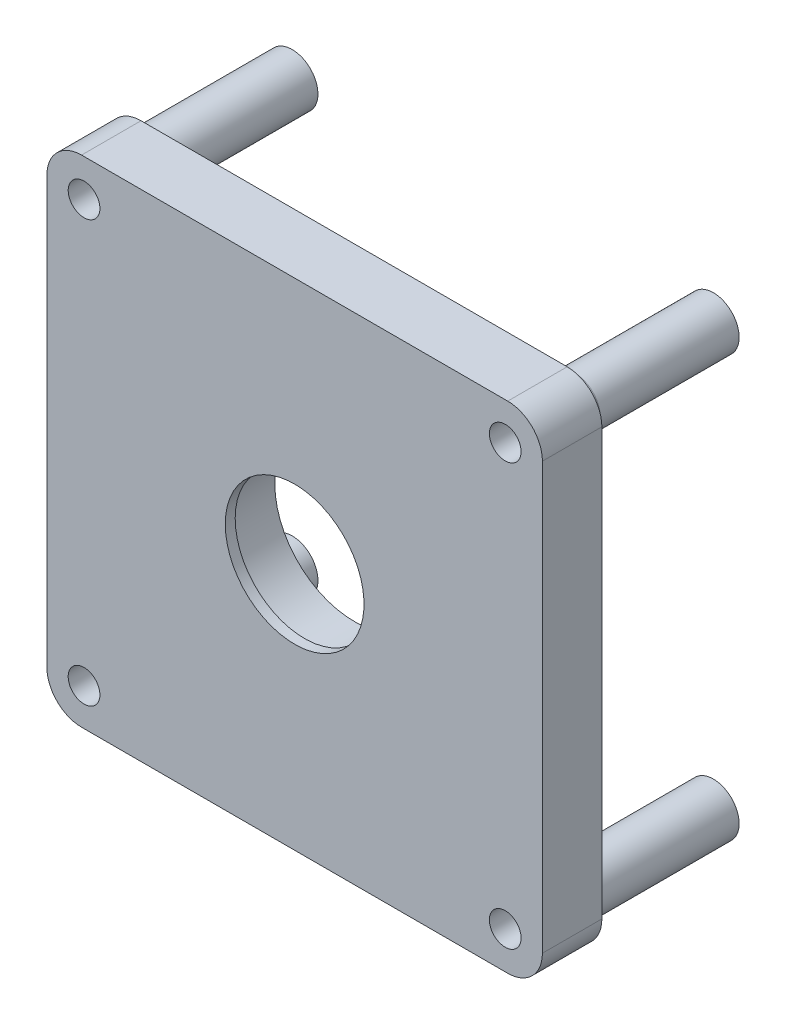
SolidWorks part; units mm, degrees
note: '?' marks a value the reader was unsure of.
ref_plane "Front Plane" through (0, 0, 0) normal (0, 0, 1) x (1, 0, 0)
ref_plane "Top Plane" through (0, 0, 0) normal (0, 1, 0) x (1, 0, 0)
ref_plane "Right Plane" through (0, 0, 0) normal (1, 0, 0) x (0, 0, -1)
ref_axis "Shaft Axis" through (0, 0, -0.635) along (0, 0, 1)?
sketch "Sketch2" plane through (0, 0, 0) normal (0, 0, 1) x (1, 0, 0)
  line L1 (-50, -50) -> (50, -50)
  line L2 (-50, -50) -> (-50, 50)
  line L3 (-50, 50) -> (50, 50)
  line L4 (50, -50) -> (50, 50)
  line L5 (-50, -50) -> (50, 50) construction
  line L6 (-50, 50) -> (50, -50) construction
  point P0 (0, 0)
  dimension "D1" = 100
extrude "Boss-Extrude1" add sketch "Sketch2" along normal blind 12
sketch "Sketch3" plane through (0, 0, 0) normal (0, 0, -1) x (-1, 0, 0)
  circle A0 centre (0, 0) radius 16
  dimension "D1" = 32
extrude "Cut-Extrude1" cut sketch "Sketch3" against normal blind 10
sketch "Sketch14" plane through (0, 0, 12) normal (0, 0, 1) x (1, 0, 0)
  circle A0 centre (0, 0) radius 65
  dimension "D1" = 130
extrude "Cut-Extrude2" [suppressed] cut sketch "Sketch14" against normal blind 2 flip side to cut
hole_wizard "7/16 Clearance Hole1" [suppressed] positions "Sketch7" profile "Sketch8" hole size "7/16" standard "ANSI Inch"
sketch "Sketch7" [suppressed] plane through (0, 0, 10.7) normal (0, 0, 1) x (1, 0, 0)
  line L1 (-58.7375, -58.7375) -> (58.7375, -58.7375) construction
  line L2 (-58.7375, -58.7375) -> (-58.7375, 58.7375) construction
  line L3 (-58.7375, 58.7375) -> (58.7375, 58.7375) construction
  line L4 (58.7375, -58.7375) -> (58.7375, 58.7375) construction
  line L5 (-58.7375, -58.7375) -> (58.7375, 58.7375) construction
  line L6 (-58.7375, 58.7375) -> (58.7375, -58.7375) construction
  line L7 (-76.2, 76.2) -> (76.2, -76.2) construction
  line L8 (76.2, -76.2) -> (76.2, 76.2) construction
  line L9 (76.2, 76.2) -> (-76.2, -76.2) construction
  point P2 (58.7375, 58.7375)
  point P35 (-58.7375, -58.7375)
  point P36 (-58.7375, 58.7375)
  point P37 (58.7375, -58.7375)
  dimension "D1" = 117.475
sketch "Sketch8" plane through (58.7375, 58.7375, 10.7) normal (1, 0, 0) x (0, -1, 0)
  line L0 (0, 0) -> (0, 10.7)
  line L1 (0, 10.7) -> (6.1519, 10.7)
  line L2 (6.1519, 10.7) -> (6.1519, 0)
  line L5 (6.1519, 0) -> (0, 0)
  line L11 (0, -6.35) -> (0, 107.95) construction
  dimension "Thru Hole Dia." = 12.3038
  dimension "Thru Hole Depth" = 10.7
hole_wizard "M6 Clearance Hole1" positions "Sketch13" profile "Sketch12" hole size "M6" standard "ANSI Metric" end condition through all
sketch "Sketch13" plane through (0, 0, 12) normal (0, 0, -1) x (-1, 0, 0)
  line L1 (-42.5, -42.5) -> (42.5, -42.5) construction
  line L2 (-42.5, -42.5) -> (-42.5, 42.5) construction
  line L3 (-42.5, 42.5) -> (42.5, 42.5) construction
  line L4 (42.5, -42.5) -> (42.5, 42.5) construction
  line L5 (-42.5, -42.5) -> (42.5, 42.5) construction
  line L6 (-42.5, 42.5) -> (42.5, -42.5) construction
  line L22 (50, -50) -> (50, 50)
  line L24 (50, 50) -> (-50, -50) construction
  line L26 (-50, 50) -> (50, -50) construction
  line L43 (-50, 50) -> (-50, -50)
  line L44 (-50, 50) -> (-50, -50)
  line L45 (50, 50) -> (-50, 50)
  line L46 (50, 50) -> (-50, 50)
  line L47 (50, -50) -> (50, 50)
  line L48 (50, -50) -> (50, 50)
  line L49 (-50, -50) -> (50, -50)
  line L50 (-50, -50) -> (50, -50)
  point P2 (42.5, 42.5)
  point P61 (-42.5, -42.5)
  point P62 (-42.5, 42.5)
  point P63 (42.5, -42.5)
  dimension "D1" = 85
  dimension "D2" = 0
sketch "Sketch12" plane through (-42.5, 42.5, 12) normal (1, 0, 0) x (0, -1, 0)
  line L0 (0, 0) -> (0, 12)
  line L1 (0, 12) -> (3.2, 12)
  line L2 (3.2, 12) -> (3.2, 0)
  line L5 (3.2, 0) -> (0, 0)
  line L11 (0, -6.35) -> (0, 107.95) construction
  dimension "Thru Hole Dia." = 6.4
  dimension "Thru Hole Depth" = 12
sketch "Sketch17" plane through (0, 0, 0) normal (0, 0, -1) x (-1, 0, 0)
  circle A0 centre (-42.5, 42.5) radius 5.2
  circle A1 centre (-42.5, 42.5) radius 3.2 construction
  circle A2 centre (-42.5, 42.5) radius 3.2
  dimension "D1" = 2
extrude "Boss-Extrude2" add sketch "Sketch17" along normal blind 30
pattern_circular "CirPattern1" count 4 over 360 about axis through (0, 0, 0) along (0, 0, 1) of "Boss-Extrude2"
sketch "Sketch18" plane through (0, 0, 0) normal (0, 0, -1) x (-1, 0, 0)
  circle A0 centre (0, 0) radius 14
  dimension "D1" = 28
extrude "Cut-Extrude3" cut sketch "Sketch18" against normal through all
fillet "Fillet1" radius 2 4 edges at (37.3, 42.5, 0) (-42.5, 37.3, 0) (-37.3, -42.5, 0) (42.5, -37.3, 0)
fillet "Fillet2" radius 7 4 edges at (-50, -50, 6) (50, -50, 6) (50, 50, 6) (-50, 50, 6)
sketch "Sketch24" [suppressed] plane through (0, 0, 12) normal (0, 0, 1) x (1, 0, 0)
  line L1 (-44.4006, 48.0738) -> (-48.2774, 43.6409)
  line L2 (-48.2774, 43.6409) -> (-46.3768, 38.0671)
  line L3 (-46.3768, 38.0671) -> (-40.5994, 36.9262)
  line L4 (-40.5994, 36.9262) -> (-36.7226, 41.3591)
  line L5 (-36.7226, 41.3591) -> (-38.6232, 46.9329)
  line L6 (-38.6232, 46.9329) -> (-44.4006, 48.0738)
  circle A0 centre (-42.5, 42.5) radius 5.1 construction
  dimension "D1" = 10.2
extrude "Cut-Extrude6" [suppressed] cut sketch "Sketch24" against normal blind 4
pattern_circular "CirPattern2" [suppressed] count 4 over 360 about axis through (0, 0, -0.635) along (0, 0, 1)
